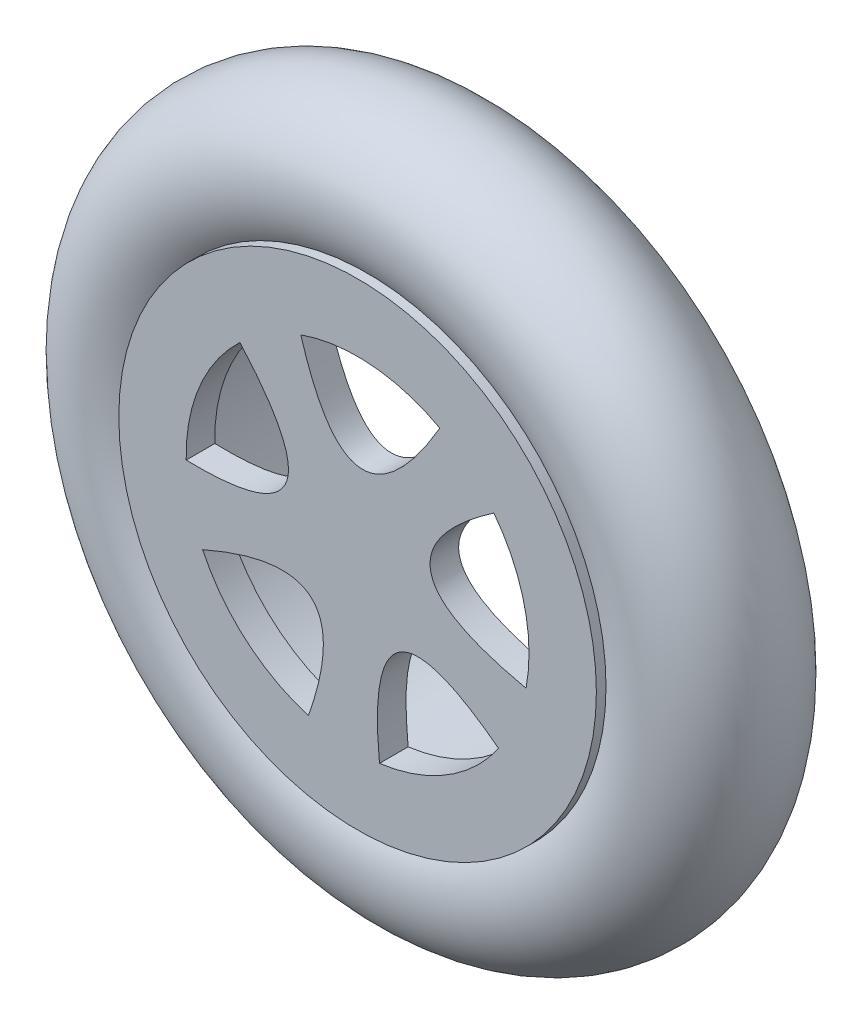
SolidWorks part; units mm, degrees
ref_plane "Front Plane" through (0, 0, 0) normal (0, 0, 1) x (1, 0, 0)
ref_plane "Top Plane" through (0, 0, 0) normal (0, 1, 0) x (1, 0, 0)
ref_plane "Right Plane" through (0, 0, 0) normal (1, 0, 0) x (0, 0, -1)
sketch "Sketch1" plane through (0, 0, 0) normal (0, 0, 1) x (1, 0, 0)
  circle A0 centre (0, 0) radius 123.825
  dimension "D1" = 247.65
extrude "Extrude1" add sketch "Sketch1" along normal blind 76.2
sketch "Sketch2" plane through (0, 0, 0) normal (0, 0, -1) x (-1, 0, 0)
  line L1 (0, 39.6863) -> (-37.744, 12.2638)
  line L2 (-37.744, 12.2638) -> (-23.327, -32.1069)
  line L3 (-23.327, -32.1069) -> (23.327, -32.1069)
  line L4 (23.327, -32.1069) -> (37.744, 12.2638)
  line L5 (37.744, 12.2638) -> (0, 39.6863)
  line L6 (-7.2268, 88.6058) -> (-42.6412, 78.006)
  line L7 (-42.6412, 78.006) -> (-70.6826, 53.9183)
  line L8 (-70.6826, 53.9183) -> (-86.5023, 20.5076)
  line L9 (-86.5023, 20.5076) -> (-87.365, -16.449)
  line L10 (-87.365, -16.449) -> (-73.1215, -50.5615)
  line L11 (-73.1215, -50.5615) -> (-46.2346, -75.9314)
  line L12 (-46.2346, -75.9314) -> (-11.3533, -88.1721)
  line L13 (-11.3533, -88.1721) -> (25.491, -85.167)
  line L14 (25.491, -85.167) -> (57.9278, -67.4358)
  line L15 (57.9278, -67.4358) -> (80.3482, -38.0443)
  line L16 (0, 58.4219) -> (-55.5625, 18.0534)
  line L17 (-55.5625, 18.0534) -> (-34.3395, -47.2643)
  line L18 (-34.3395, -47.2643) -> (34.3395, -47.2643)
  line L19 (34.3395, -47.2643) -> (55.5625, 18.0534)
  line L20 (55.5625, 18.0534) -> (0, 58.4219)
  line L21 (80.3482, -38.0443) -> (88.8758, -2.0746)
  line L22 (88.8758, -2.0746) -> (82.0359, 34.2538)
  line L23 (82.0359, 34.2538) -> (61.0113, 64.6594)
  line L24 (61.0113, 64.6594) -> (29.4372, 83.8848)
  line L25 (29.4372, 83.8848) -> (-7.2268, 88.6058)
  circle A0 centre (0, 0) radius 88.9
  circle A1 centre (0, 0) radius 32.1069 construction
  circle A2 centre (0, 0) radius 86.9573 construction
  circle A3 centre (0, 0) radius 47.2643 construction
  spline S0 degree 2 poles (-42.6412, 78.006) (3.8595, -1.919) (29.4372, 83.8848) knots 0 0 0 1 1 1
  spline S1 degree 2 poles (61.0113, 64.6594) (-0.6324, -4.2636) (88.8758, -2.0746) knots 0 0 0 1 1 1
  spline S2 degree 2 poles (80.3482, -38.0443) (-4.2504, -0.7161) (25.491, -85.167) knots 0 0 0 1 1 1
  spline S3 degree 2 poles (-11.3533, -88.1721) (-1.9945, 3.821) (-73.1215, -50.5615) knots 0 0 0 1 1 1
  spline S4 degree 2 poles (-87.365, -16.449) (3.0177, 3.0776) (-70.6826, 53.9183) knots 0 0 0 1 1 1
sketch "Sketch4" plane through (0, 0, 0) normal (0, 1, 0) x (1, 0, 0)
  line L0 (123.825, -76.2) -> (123.825, 0) construction
  line L1 (123.825, -5) -> (106.3698, -5)
  line L2 (123.825, -5) -> (123.825, -71.2)
  line L3 (123.825, -71.2) -> (106.3698, -71.2)
  line L4 (106.3698, -5) -> (106.3698, -71.2)
  line L5 (123.825, 0) -> (-123.825, 0) construction
  line L6 (-123.825, -76.2) -> (123.825, -76.2) construction
  line L7 (0, 0) -> (0, -100.868) construction
  dimension "D1" = 5
  dimension "D2" = 5
  dimension "D3" = 17.4552
revolve "Cut-Revolve1" cut sketch "Sketch4" angle 360 about L7
extrude "Extrude7" cut sketch "Sketch2" against normal through all contours L9 S4 L17 L16 L8 | L8 A0 | L9 A0 | L17 S4 L16 | L12 S3 L18 L17 L11 | L18 S3 L17 | L11 A0 | L12 A0 | L15 A0 | L15 S2 L19 L18 L14 | L19 S2 L18 | L14 A0 | L23 S1 L20 L19 L22 | L20 S1 L19 | L23 A0 | L22 A0 | L6 S0 L16 L20 L25 | L6 A0 | L16 S0 L20 | L25 A0 region at (1.5385, 47.6422, 0) region at (45.7858, 13.2591, 0) region at (-44.835, 16.1854, 0) region at (5.3368, 69.9054, 0) region at (26.7587, -39.4476, 0) region at (68.1331, 16.5263, 0) region at (-29.248, -37.639, 0) region at (-64.8348, 26.6776, 0) region at (25.157, 84.051, 0) region at (-11.2045, 87.0167, 0) region at (36.7718, -59.6916, 0) region at (87.7112, 2.0474, 0) region at (79.2954, 37.5458, 0) region at (-45.4069, -53.4178, 0) region at (-72.1633, 49.899, 0) region at (-86.2202, 16.2335, 0) region at (29.0515, -82.7856, 0) region at (60.2118, -63.8121, 0) region at (-69.7564, -53.2118, 0) region at (-42.0825, -76.9839, 0)
sketch "Sketch5" plane through (0, 0, 0) normal (0, 1, 0) x (1, 0, 0)
  line L0 (-123.825, -71.2) -> (-106.3698, -71.2)
  line L1 (123.825, -71.2) -> (-123.825, -71.2) construction
  line L2 (106.3698, -71.2) -> (-106.3698, -71.2) construction
  line L3 (-106.3698, -71.2) -> (-106.3698, -5)
  line L4 (-106.3698, -5) -> (106.3698, -5) construction
  line L5 (-106.3698, -5) -> (-123.825, -5)
  arc A0 (-123.825, -5) -> (-123.825, -71.2) centre (-144.4698, -38.1) ccw
  dimension "D1" = 38.1
  dimension "D2" = 17.4552
sketch "Sketch6" plane through (0, 0, 0) normal (1, 0, 0) x (0, 0, -1)
  line L0 (0, 0) -> (-61.3571, 0)
revolve "Revolve1" add sketch "Sketch5" angle 360 about L0
sketch "Sketch8" plane through (0, 0, 0) normal (0, 0, -1) x (-1, 0, 0)
  circle A0 centre (0, 0) radius 103.8766
extrude "Extrude8" cut sketch "Sketch8" against normal up to vertex (61.3571 mm away) up to point (0, 0, 61.3571)
